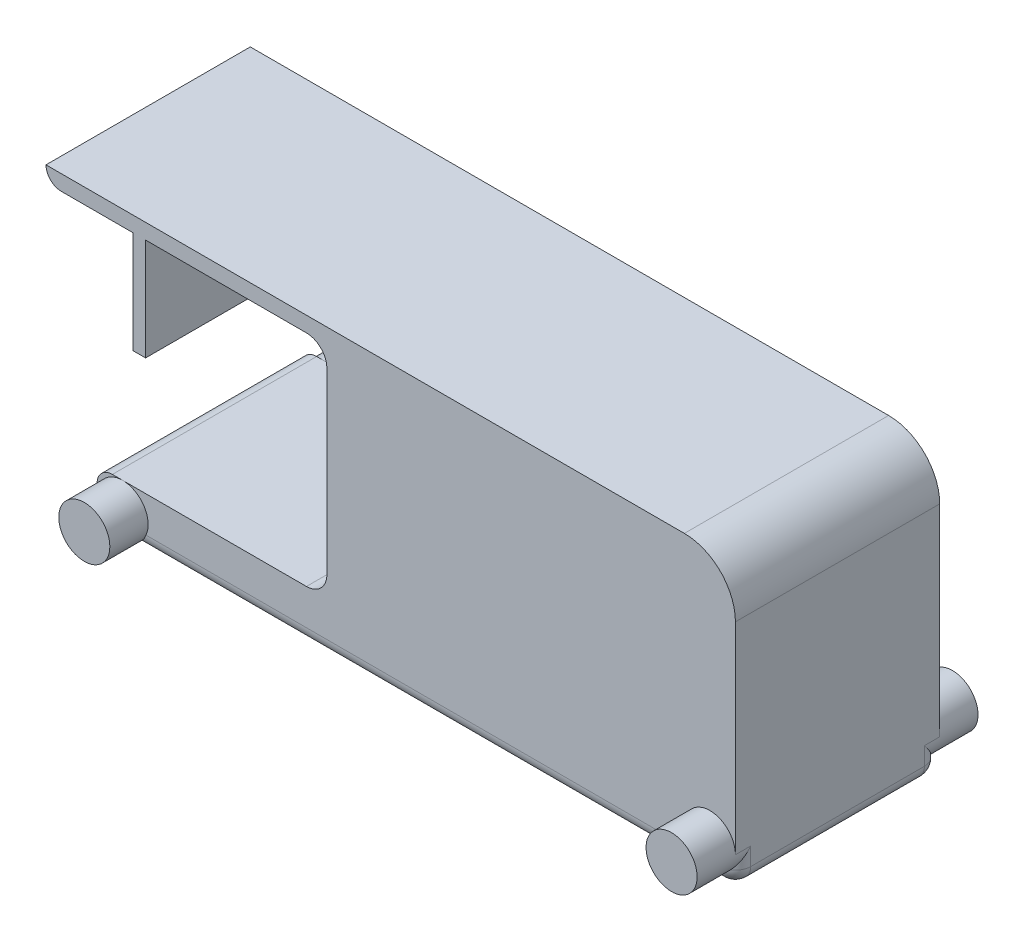
SolidWorks part; units mm, degrees
ref_plane "Alzado" through (0, 0, 0) normal (0, 0, 1) x (1, 0, 0)
ref_plane "Planta" through (0, 0, 0) normal (0, 1, 0) x (1, 0, 0)
ref_plane "Vista lateral" through (0, 0, 0) normal (1, 0, 0) x (0, 0, -1)
sketch "Croquis1" plane through (0, 0, 0) normal (0, 1, 0) x (1, 0, 0)
  line L1 (550, 200) -> (-700, 200)
  line L2 (550, 200) -> (550, -200)
  line L3 (550, -200) -> (-700, -200)
  line L4 (-700, 200) -> (-700, -200)
  dimension "D1" = 400
  dimension "D2" = 1250
  dimension "D3" = 550
  dimension "D4" = 200
extrude "Saliente-Extruir1" add sketch "Croquis1" along normal blind 100
sketch "Croquis2" plane through (0, 100, 0) normal (0, 1, 0) x (1, 0, 0)
  line L0 (-700, 200) -> (-700, -200) construction
  line L4 (-250, -200) -> (550, -200)
  line L5 (-250, -200) -> (-250, 200)
  line L6 (-250, 200) -> (550, 200)
  line L7 (550, -200) -> (550, 200)
  dimension "D1" = 450
  dimension "D2" = 400
  dimension "D3" = 800
  dimension "D4" = 200
extrude "Saliente-Extruir2" add sketch "Croquis2" along normal blind 460
fillet "Redondeo1" radius 100 1 edges at (550, 560, 0)
sketch "Croquis3" plane through (0, 0, 200) normal (0, 0, 1) x (1, 0, 0)
  line L0 (-250, 560) -> (-700, 560)
  line L1 (-700, 560) -> (-800, 560)
  line L2 (-800, 560) -> (-800, 530)
  line L3 (-800, 530) -> (-700, 530)
  line L4 (-700, 530) -> (-250, 530)
  line L5 (-250, 560) -> (-250, 100) construction
  line L6 (-250, 530) -> (-250, 560)
  line L7 (-700, 100) -> (-700, 0) construction
  line L8 (-700, 560) -> (-700, 530) construction
  line L9 (-700, 100) -> (-250, 100) construction
  dimension "D1" = 100
  dimension "D2" = 30
  dimension "D3" = 100
  dimension "D4" = 430
extrude "Saliente-Extruir3" add sketch "Croquis3" against normal blind 400
fillet "Redondeo2" radius 40 1 edges at (-250, 100, 0)
fillet "Redondeo3" radius 40 1 edges at (-250, 530, 0)
sketch "Croquis4" plane through (0, 560, 0) normal (0, 1, 0) x (1, 0, 0)
  line L0 (550, 200) -> (550, -200) construction
  line L1 (-120, 200) -> (220, 200)
  line L2 (-120, 200) -> (-120, -200)
  line L3 (-120, -200) -> (220, -200)
  line L4 (220, 200) -> (220, -200)
  dimension "D1" = 340
  dimension "D2" = 400
  dimension "D3" = 200
  dimension "D4" = 330
sketch "Croquis5" plane through (0, 0, 200) normal (0, 0, 1) x (1, 0, 0)
  line L0 (-700, 100) -> (-290, 100) construction
  line L1 (-700, 100) -> (-700, 0) construction
  line L2 (550, 460) -> (550, 0) construction
  line L4 (-700, 0) -> (550, 0) construction
  circle A0 centre (500, 65) radius 50
  circle A1 centre (-650, 50) radius 50
  dimension "D2" = 100
  dimension "D4" = 100
  dimension "D1" = 50
  dimension "D3" = 50
  dimension "D5" = 50
  dimension "D6" = 65
extrude "Saliente-Extruir4" add sketch "Croquis5" along normal blind 75
sketch "Croquis6" plane through (0, 0, -200) normal (0, 0, -1) x (1, 0, 0)
  line L0 (550, 0) -> (-700, 0) construction
  line L1 (-700, -100) -> (-700, 0) construction
  line L2 (550, -460) -> (550, 0) construction
  circle A0 centre (-650, -50) radius 50
  circle A1 centre (500, -65) radius 50
  dimension "D1" = 100
  dimension "D6" = 100
  dimension "D2" = 50
  dimension "D3" = 50
  dimension "D4" = 50
  dimension "D5" = 65
extrude "Saliente-Extruir5" add sketch "Croquis6" along normal blind 75
fillet "Redondeo9" radius 30 1 edges at (-700, 0, 0)
fillet "Redondeo10" radius 30 1 edges at (-700, 100, 0)
fillet "Redondeo11" radius 30 1 edges at (550, 0, 0)
fillet "Redondeo12" radius 30 3 edges at (-800, 545, -200) (-800, 530, 0) (-800, 545, 200)
fillet "Redondeo13" radius 30 3 edges at (541.2132, 8.7868, 200) (550, 47.5, 200) (-65, 0, 200)
fillet "Redondeo14" radius 30 3 edges at (-65, 0, -200) (541.2132, 8.7868, -200) (550, 47.5, -200)
sketch "Croquis7" plane through (0, 530, 0) normal (0, -1, 0) x (1, 0, 0)
  line L0 (-770, 200) -> (-290, 200) construction
  line L1 (-630, 200) -> (-605, 200)
  line L2 (-630, 200) -> (-630, -200)
  line L3 (-630, -200) -> (-605, -200)
  line L4 (-605, 200) -> (-605, -200)
  line L5 (-770, -200) -> (-290, -200) construction
  line L6 (-770, 200) -> (-770, -200) construction
  dimension "D1" = 25
  dimension "D2" = 140
extrude "Saliente-Extruir6" add sketch "Croquis7" along normal blind 200
